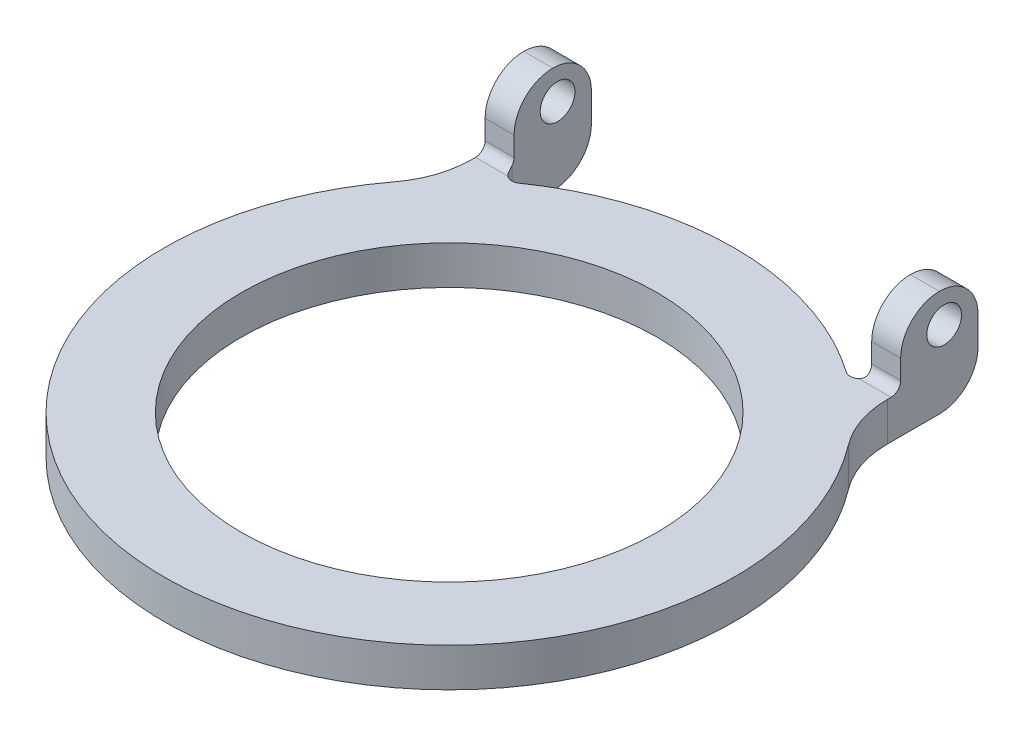
SolidWorks part; units mm, degrees
ref_plane "Front Plane" through (0, 0, 0) normal (0, 0, 1) x (1, 0, 0)
ref_plane "Top Plane" through (0, 0, 0) normal (0, 1, 0) x (1, 0, 0)
ref_plane "Right Plane" through (0, 0, 0) normal (1, 0, 0) x (0, 0, -1)
sketch "Sketch1" plane through (0, 0, 0) normal (0, 1, 0) x (1, 0, 0)
  line L0 (-11.5, 33.2132) -> (-11.5, 24.98) construction
  line L1 (-17.5, 21.2132) -> (17.5, 21.2132) construction
  line L2 (-17.5, 21.2132) -> (-17.5, 33.2132) construction
  line L3 (-17.5, 33.2132) -> (17.5, 33.2132) construction
  line L4 (17.5, 21.2132) -> (17.5, 33.2132) construction
  line L6 (11.5, 33.2132) -> (11.5, 24.98) construction
  line L7 (-18.5, 33.2132) -> (-21.5, 33.2132)
  line L8 (-18.5, 33.2132) -> (-18.5, 17.1464)
  line L9 (-18.5, 17.1464) -> (-21.5, 17.1464)
  line L10 (-21.5, 33.2132) -> (-21.5, 17.1464)
  line L11 (18.5, 33.2132) -> (21.5, 33.2132)
  line L12 (18.5, 33.2132) -> (18.5, 17.1464)
  line L13 (18.5, 17.1464) -> (21.5, 17.1464)
  line L14 (21.5, 33.2132) -> (21.5, 17.1464)
  line L15 (-10.5, 33.2132) -> (-7.5, 33.2132)
  line L16 (-10.5, 33.2132) -> (-10.5, 25.4165)
  line L17 (-10.5, 25.4165) -> (-7.5, 25.4165)
  line L18 (-7.5, 33.2132) -> (-7.5, 25.4165)
  line L19 (7.5, 33.2132) -> (10.5, 33.2132)
  line L20 (7.5, 33.2132) -> (7.5, 25.4165)
  line L21 (7.5, 25.4165) -> (10.5, 25.4165)
  line L22 (10.5, 33.2132) -> (10.5, 25.4165)
  circle A0 centre (0, 0) radius 27.5 construction
  circle A1 centre (0, 0) radius 29.5
  dimension "D1" = 55
  dimension "D11" = 2
  dimension "D2" = 35
  dimension "D3" = 12
  dimension "D4" = 6
  dimension "D5" = 6
  dimension "D6" = 1
  dimension "D7" = 1
  dimension "D8" = 1
  dimension "D9" = 1
  dimension "D10" = 3
extrude "Boss-Extrude1" add sketch "Sketch1" along normal blind 4 contours L12 A0 L21 L20 L18 L17 L8 L9 L13 | L8 A0 L9 | A0 L8 L7 L10 | L18 A0 L17 | L21 A0 L20 | L13 A0 L12 | A0 L14 L11 L12 region at (-20.06, 0, -27.4054) region at (0, 0, 0.3545) region at (-19.8461, 0, -19.471) region at (-8.9097, 0, -26.7622) region at (20.06, 0, -27.4054) region at (19.8461, 0, -19.471) region at (8.9097, 0, -26.7622)
sketch "Sketch2" plane through (0, 4, 0) normal (0, 1, 0) x (1, 0, 0)
  line L0 (-18.5, 33.2132) -> (-18.5, 22.9783) construction
  line L1 (-21.5, 33.2132) -> (-18.5, 33.2132)
  line L2 (-21.5, 33.2132) -> (-21.5, 20.199)
  line L4 (-18.5, 33.2132) -> (-18.5, 22.9783)
  line L13 (18.5, 33.2132) -> (21.5, 33.2132)
  line L14 (18.5, 33.2132) -> (18.5, 22.9783)
  line L16 (21.5, 33.2132) -> (21.5, 20.199)
  line L17 (-18.5, 33.2132) -> (-21.5, 33.2132) construction
  line L19 (21.5, 33.2132) -> (21.5, 20.199) construction
  line L20 (-21.5, 25.2132) -> (21.5, 25.2132)
  arc A0 (21.5, 20.199) -> (18.5, 22.9783) centre (0, 0) ccw
  arc A3 (-18.5, 22.9783) -> (-21.5, 20.199) centre (0, 0) ccw
  arc A6 (-21.5, 20.199) -> (21.5, 20.199) centre (0, 0) ccw construction
  point P5 (-21.5, 17.1464)
  point P7 (-21.5, 20.199)
  line M28 (-18.5, 33.2132) -> (-21.5, 33.2132)
  line M29 (-21.5, 33.2132) -> (-21.5, 20.199)
  line M32 (21.5, 33.2132) -> (18.5, 33.2132)
  line M33 (18.5, 33.2132) -> (18.5, 22.9783)
  dimension "D1" = 8
extrude "Boss-Extrude2" add sketch "Sketch2" along normal blind 7 contours L20 L4 M29 M28 | L20 L16 M33 M32 region at (20, 4, -29.2132) region at (-20, 4, -29.2132)
sketch "Sketch3" plane through (-21.5, 0, 0) normal (-1, 0, 0) x (0, 0, 1)
  line L0 (-33.2132, 11) -> (-33.2132, 0) construction
  line L1 (-25.2132, 4) -> (-25.2132, 11.5)
  line L2 (-25.2132, 7.75) -> (-33.2132, 7.75) construction
  circle A0 centre (-29.7132, 7.75) radius 1.8
  point P9 (-29.7132, 7.75)
  dimension "D1" = 3.6
  dimension "D2" = 3.5
  dimension "D3" = 7.5
extrude "Cut-Extrude1" cut sketch "Sketch3" against normal through all contours A0
fillet "Fillet1" radius 4 6 edges at (-20, 11, -25.2132) (-20, 11, -33.2132) (20, 11, -25.2132) (20, 11, -33.2132) (20, 0, -33.2132) (-20, 0, -33.2132)
fillet "Fillet2" radius 10 2 edges at (21.5, 2, -20.199) (-21.5, 2, -20.199)
fillet "Fillet3" radius 1 2 edges at (-18.5, 2, -22.9783) (18.5, 2, -22.9783)
fillet "Fillet4" radius 1 2 edges at (-20, 4, -25.2132) (20, 4, -25.2132)
sketch "Sketch4" plane through (0, 0, 0) normal (0, -1, 0) x (1, 0, 0)
  circle A1 centre (0, 0) radius 21.5
  arc A3 (21.5, 20.199) -> (-21.5, -20.199) centre (0, 0) ccw construction
  point P6 (0, 0)
  dimension "D1" = 8
extrude "Cut-Extrude2" cut sketch "Sketch4" against normal through all contours A1
